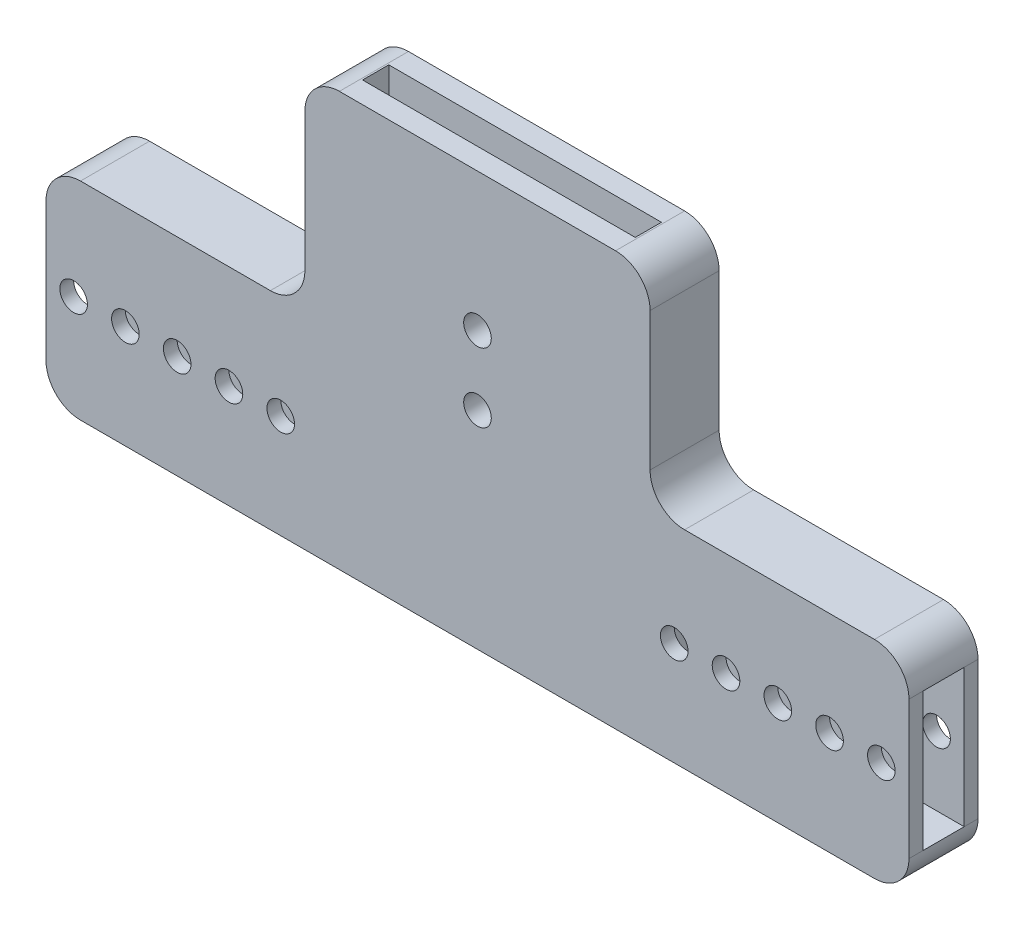
SolidWorks part; units mm, degrees
ref_plane "Front Plane" through (0, 0, 0) normal (0, 0, 1) x (1, 0, 0)
ref_plane "Top Plane" through (0, 0, 0) normal (0, 1, 0) x (1, 0, 0)
ref_plane "Right Plane" through (0, 0, 0) normal (1, 0, 0) x (0, 0, -1)
sketch "Sketch1" plane through (0, 0, 0) normal (0, 0, 1) x (1, 0, 0)
  line L1 (-25, 30) -> (25, 30)
  line L2 (-25, 30) -> (-25, -30)
  line L3 (-25, -30) -> (25, -30)
  line L4 (25, 30) -> (25, -30)
  line L5 (-25, 30) -> (25, -30) construction
  line L6 (-25, -30) -> (25, 30) construction
  point P0 (0, 0)
extrude "Boss-Extrude1" add sketch "Sketch1" along normal blind 10
sketch "Sketch2" plane through (0, 30, 0) normal (0, 1, 0) x (1, 0, 0)
  line L0 (25, 0) -> (-25, 0) construction
  line L1 (-19.75, -3.1) -> (19.75, -3.1)
  line L2 (-19.75, -3.1) -> (-19.75, -6.9)
  line L3 (-19.75, -6.9) -> (19.75, -6.9)
  line L4 (19.75, -3.1) -> (19.75, -6.9)
  line L5 (-19.75, -3.1) -> (19.75, -6.9) construction
  line L6 (-19.75, -6.9) -> (19.75, -3.1) construction
  line L7 (25, -10) -> (-25, -10) construction
  line L9 (-25, -10) -> (-25, 0) construction
  line L10 (25, -10) -> (25, 0) construction
  point P0 (0, -5)
  dimension "D1" = 3.1
  dimension "D2" = 3.1
  dimension "D3" = 5.25
  dimension "D4" = 5.25
extrude "Cut-Extrude1" cut sketch "Sketch2" against normal through all
sketch "Sketch3" plane through (-25, 0, 0) normal (-1, 0, 0) x (0, 0, 1)
  line L0 (10, 30) -> (10, -30) construction
  line L1 (0, -30) -> (10, -30)
  line L2 (0, -30) -> (0, 0)
  line L3 (0, 0) -> (10, 0)
  line L4 (10, -30) -> (10, 0)
  line L5 (5, 0) -> (5, -30) construction
  line L6 (0, -15) -> (10, -15) construction
  point P1024 (5, -15)
  dimension "D1" = 30
extrude "Boss-Extrude2" add sketch "Sketch3" along normal blind 37.5
sketch "Sketch4" plane through (-62.5, 0, 0) normal (-1, 0, 0) x (0, 0, 1)
  line L0 (10, 0) -> (0, 0) construction
  line L1 (2, -5) -> (8, -5)
  line L2 (2, -5) -> (2, -25)
  line L3 (2, -25) -> (8, -25)
  line L4 (8, -5) -> (8, -25)
  line L5 (2, -5) -> (8, -25) construction
  line L6 (2, -25) -> (8, -5) construction
  line L7 (10, -30) -> (10, 0) construction
  line L8 (0, 0) -> (0, -30) construction
  line L9 (0, -30) -> (10, -30) construction
  point P0 (5, -15)
  dimension "D1" = 5
  dimension "D2" = 2
  dimension "D3" = 2
  dimension "D4" = 5
extrude "Cut-Extrude2" cut sketch "Sketch4" against normal blind 37.5
sketch "Sketch5" plane through (0, 0, 10) normal (0, 0, 1) x (1, 0, 0)
  line L0 (-62.5, -5) -> (-62.5, -25) construction
  circle A0 centre (-58.5, -14.9958) radius 2
  circle A1 centre (-51, -14.9958) radius 2
  circle A2 centre (-43.5, -14.9958) radius 2
  circle A3 centre (-36, -14.9958) radius 2
  circle A4 centre (-28.5, -14.9958) radius 2
  dimension "D1" = 5
  dimension "D2" = 4
extrude "Cut-Extrude3" cut sketch "Sketch5" against normal blind 35
mirror "Mirror1" about plane through (0, 0, 0) normal (1, 0, 0) of "Cut-Extrude3", "Cut-Extrude2", "Boss-Extrude2"
fillet "Fillet1" radius 5 8 edges at (62.5, -30, 5) (62.5, 0, 5) (25, 0, 5) (-62.5, -30, 5) (-62.5, 0, 5) (-25, 0, 5) (25, 30, 5) (-25, 30, 5)
sketch "Sketch6" plane through (0, 0, 10) normal (0, 0, 1) x (1, 0, 0)
  circle A0 centre (0, 0) radius 2
  circle A1 centre (0, 10) radius 2
  dimension "D1" = 10
extrude "Cut-Extrude4" cut sketch "Sketch6" against normal blind 35
